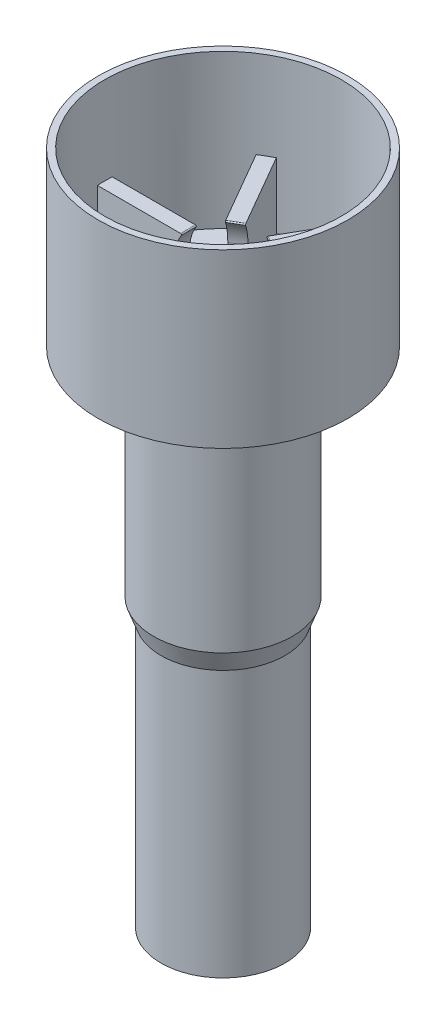
SolidWorks part; units mm, degrees
material "PET"
ref_plane "Front Plane" through (0, 0, 0) normal (0, 0, 1) x (1, 0, 0)
ref_plane "Top Plane" through (0, 0, 0) normal (0, 1, 0) x (1, 0, 0)
ref_plane "Right Plane" through (0, 0, 0) normal (1, 0, 0) x (0, 0, -1)
sketch "Sketch1" plane through (0, 0, 0) normal (0, 0, 1) x (1, 0, 0)
  line L0 (0, 0) -> (0, 36.5) construction
  line L1 (0, 36.5) -> (-6.4, 36.5) construction
  line L2 (0, 0) -> (-2.15, 0) construction
  line L3 (-6.4, 36.5) -> (-6.4, 28.2)
  line L4 (-6.4, 28.2) -> (-2.1, 28.2)
  line L5 (-2.1, 28.2) -> (-2.1, 24)
  line L6 (-2.1, 24) -> (-1.5, 24)
  line L7 (-1.5, 24) -> (-1.5, 23)
  line L8 (-1.5, 23) -> (-2.15, 23)
  line L9 (-2.15, 23) -> (-2.15, 0)
  line L10 (-6.4, 36.5) -> (-6.75, 36.5)
  line L11 (-6.75, 36.5) -> (-6.75, 27.2)
  line L12 (-6.75, 27.2) -> (-3.75, 27.2)
  line L13 (-3.75, 27.2) -> (-3.75, 15.5)
  line L14 (-3.75, 15.5) -> (-3.35, 14.401)
  line L15 (-3.35, 14.401) -> (-3.35, 0)
  line L16 (-3.35, 0) -> (-2.15, 0)
  dimension "D1" = 36.5
  dimension "D2" = 6.4
  dimension "D3" = 2.15
  dimension "D4" = 8.3
  dimension "D5" = 4.2
  dimension "D6" = 1
  dimension "D7" = 2.1
  dimension "D8" = 1.5
  dimension "D9" = 6.75
  dimension "D10" = 1
  dimension "D11" = 11.7
  dimension "D12" = 3.75
  dimension "D13" = 20
  dimension "D14" = 3.35
revolve "Revolve1" add sketch "Sketch1" angle 360 about L0
sketch "Sketch3" plane through (0, 0, 0) normal (0, 0, 1) x (1, 0, 0)
  line L0 (-6.4, 28.2) -> (-2.1, 28.2)
  line L1 (2.1, 28.2) -> (6.4, 28.2)
  line L2 (2.1, 28.2) -> (6.4, 28.2)
  line L3 (-6.4, 28.2) -> (-2.1, 28.2) construction
  line L4 (-6.4, 36.5) -> (-6.4, 28.2)
  line L5 (6.4, 28.2) -> (6.4, 36.5)
  line L6 (6.4, 28.2) -> (6.4, 36.5)
  line L7 (-6.4, 36.5) -> (-6.4, 28.2) construction
  line L8 (-6.4, 31.75) -> (-1.8, 31.75)
  line L9 (-6.4, 31.75) -> (-6.4, 28.2)
  line L10 (-6.4, 28.2) -> (-2.2, 28.2)
  line L11 (-2.2, 28.2) -> (-2.2, 30.5)
  line L12 (6.4, 36.5) -> (-6.4, 36.5) construction
  line L13 (0, 0) -> (0, 40.0058) construction
  arc A0 (-2.2, 30.5) -> (-1.8, 31.75) centre (-0.0469, 30.5) cw
  dimension "D1" = 4.75
  dimension "D2" = 0.1
  dimension "D3" = 1.8
  dimension "D4" = 2.3
extrude "Boss-Extrude1" add sketch "Sketch3" along normal blind 0.4 and the other way blind 0.4 contours L11 A0 L8 L9 L10 region at (-4.2765, 29.9906, 0)
fillet "Fillet1" radius 0.05 1 edges at (-1.8, 31.75, 0)
sketch "Sketch4" plane through (0, 0, 0) normal (0, 0, 1) x (1, 0, 0)
  line L0 (0, 0) -> (0, 38.5674) construction
pattern_circular "CirPattern1" count 6 over 360 about axis through (0, 0, 0) along (0, 1, 0) of "Boss-Extrude1", "Fillet1" reverse direction yes
